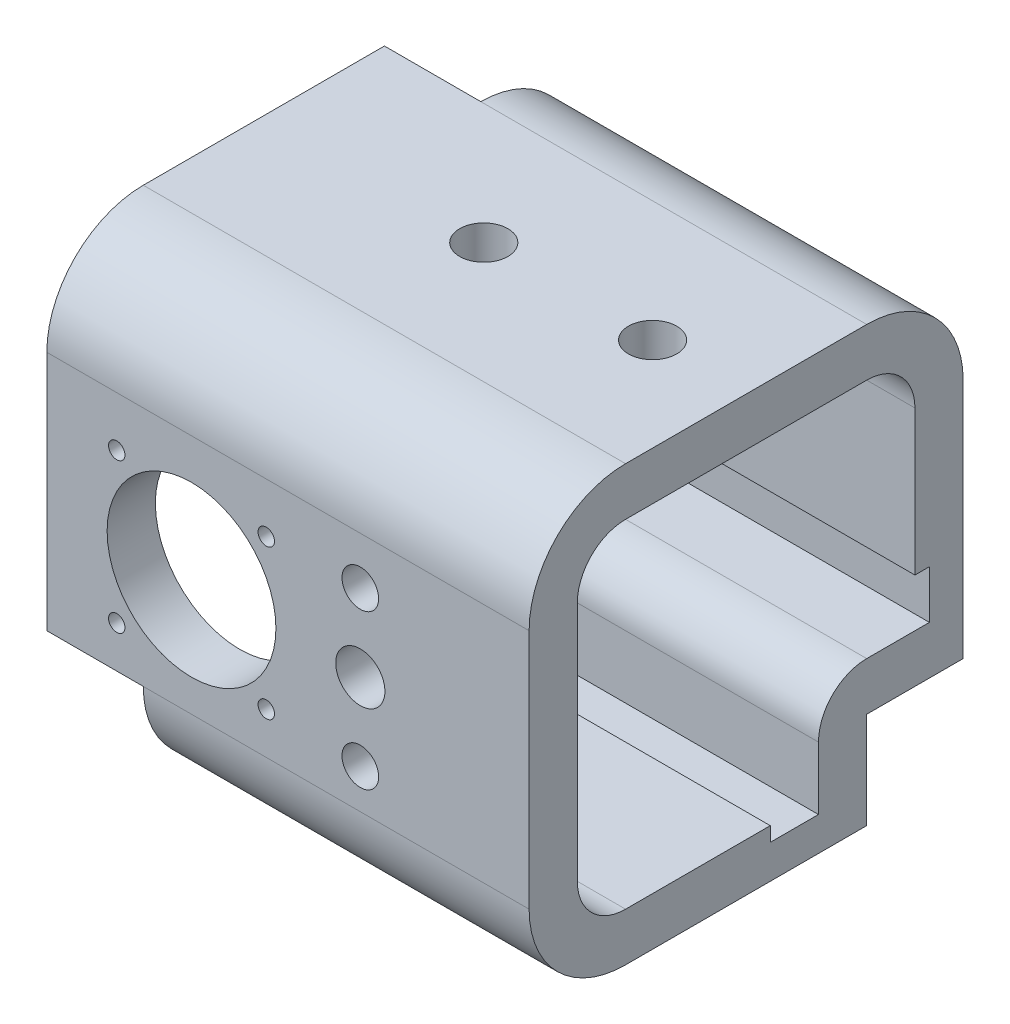
SolidWorks part; units mm, degrees
material "ABS"
ref_plane "Front Plane" through (0, 0, 0) normal (0, 0, 1) x (1, 0, 0)
ref_plane "Top Plane" through (0, 0, 0) normal (0, 1, 0) x (1, 0, 0)
ref_plane "Right Plane" through (0, 0, 0) normal (1, 0, 0) x (0, 0, -1)
sketch "Sketch2" plane through (0, 0, 0) normal (1, 0, 0) x (0, 0, -1)
  line L0 (-40.8, -13.55) -> (-40.8, -17.45) construction
  line L1 (19.2, 35.85) -> (-30.8, 35.85)
  line L2 (29.2, 25.85) -> (29.2, -24.15)
  line L3 (19.2, -34.15) -> (-30.8, -34.15)
  line L4 (-40.8, 25.85) -> (-40.8, -24.15)
  line L5 (-50.8, 15) -> (-40.8, 15) construction
  line L10 (-48.05, 15) -> (-59.05, 15) construction
  line L11 (-50.8, -15) -> (-40.8, -15) construction
  line L12 (-59.05, -15) -> (-48.05, -15) construction
  line L13 (19.2, 45.85) -> (-30.8, 45.85)
  line L14 (-50.8, 25.85) -> (-50.8, -24.15)
  line L15 (19.2, -44.15) -> (-30.8, -44.15)
  line L16 (39.2, 25.85) -> (39.2, -24.15)
  line L19 (-40.05, -21.15) -> (-29.05, -21.15) construction
  arc A0 (-30.8, 35.85) -> (-40.8, 25.85) centre (-30.8, 25.85) ccw
  arc A1 (-30.8, -34.15) -> (-40.8, -24.15) centre (-30.8, -24.15) cw
  arc A2 (19.2, -34.15) -> (29.2, -24.15) centre (19.2, -24.15) ccw
  arc A3 (19.2, 35.85) -> (29.2, 25.85) centre (19.2, 25.85) cw
  arc A4 (-30.8, 45.85) -> (-50.8, 25.85) centre (-30.8, 25.85) ccw
  arc A5 (-30.8, -44.15) -> (-50.8, -24.15) centre (-30.8, -24.15) cw
  arc A6 (19.2, -44.15) -> (39.2, -24.15) centre (19.2, -24.15) ccw
  arc A7 (19.2, 45.85) -> (39.2, 25.85) centre (19.2, 25.85) cw
  arc A8 (19.2, 35.85) -> (29.2, 25.85) centre (19.2, 25.85) cw construction
  dimension "D1" = 10
  dimension "D2" = 10
  dimension "D3" = 3
  dimension "D4" = 70
extrude "Boss-Extrude1" add sketch "Sketch2" along normal blind 70 and the other way blind 30
sketch "Sketch3" plane through (0, 0, 50.8) normal (0, 0, 1) x (1, 0, 0)
  arc A0 (-14.0466, 5.2624) -> (-13.6647, 6.1867) centre (0, 0) ccw construction
  arc A1 (-14.0466, 5.2624) -> (-13.6647, 6.1867) centre (0, 0) ccw construction
  circle A2 centre (15.5, -15.5) radius 1.7 construction
  circle A3 centre (15.5, 15.5) radius 1.7 construction
  circle A4 centre (-15.5, 15.5) radius 1.7 construction
  circle A5 centre (-15.5, -15.5) radius 1.7 construction
  circle A6 centre (15.5, -15.5) radius 1.7
  circle A7 centre (15.5, 15.5) radius 1.7
  circle A8 centre (-15.5, 15.5) radius 1.7
  circle A9 centre (-15.5, -15.5) radius 1.7
  circle A10 centre (0, 0) radius 17.5
  arc A11 (-16.3877, 6.1395) -> (-15.9422, 7.2178) centre (0, 0) ccw construction
  circle A12 centre (35, 0) radius 5.1 construction
  circle A13 centre (35, 0) radius 5.1
  circle A14 centre (35, -16) radius 3.8 construction
  circle A15 centre (35, 16) radius 3.8 construction
  circle A16 centre (35, -16) radius 3.8
  circle A17 centre (35, 16) radius 3.8
  dimension "D1" = 2.5
extrude "Cut-Extrude1" cut sketch "Sketch3" against normal up to next
sketch "Sketch4" plane through (0, 45.85, 0) normal (0, 1, 0) x (1, 0, 0)
  line L0 (50.6, -5.8) -> (15.6, -5.8) construction
  line L1 (-30, 19.2) -> (70, 19.2) construction
  line L2 (-30, -30.8) -> (70, -30.8) construction
  line L3 (28.05, -18.9) -> (38.15, -18.9) construction
  line L4 (28.05, -18.9) -> (38.15, -18.9) construction
  line L5 (33.1, -18.9) -> (33.1, -5.8) construction
  circle A0 centre (15.6, -5.8) radius 5
  circle A1 centre (50.6, -5.8) radius 5
  point P12 (33.1, -5.8)
  dimension "D1" = 10
  dimension "D2" = 35
extrude "Cut-Extrude2" cut sketch "Sketch4" against normal up to next
sketch "Sketch5" plane through (0, 0, 50.8) normal (0, 0, 1) x (1, 0, 0)
  line L0 (-30, -24.15) -> (70, -24.15) construction
  line L1 (-10, -24.15) -> (-30, -24.15)
  line L2 (-10, -24.15) -> (-10, -44.15)
  line L3 (-10, -44.15) -> (-30, -44.15)
  line L4 (-30, -24.15) -> (-30, -44.15)
  line L5 (-30, 25.85) -> (-30, -24.15) construction
  line L6 (-30, -44.15) -> (70, -44.15) construction
  dimension "D1" = 20
extrude "Cut-Extrude3" cut sketch "Sketch5" against normal through all both and the other way through all
sketch "Sketch6" plane through (0, 45.85, 0) normal (0, 1, 0) x (1, 0, 0)
  line L0 (-30, 19.2) -> (-30, -30.8) construction
  line L1 (-30, 39.2) -> (-10, 39.2)
  line L2 (-30, 39.2) -> (-30, 19.2)
  line L3 (-30, 19.2) -> (-10, 19.2)
  line L4 (-10, 39.2) -> (-10, 19.2)
  line L5 (-30, 19.2) -> (70, 19.2) construction
  line L6 (-30, 39.2) -> (70, 39.2) construction
  dimension "D1" = 20
extrude "Cut-Extrude4" cut sketch "Sketch6" against normal through all
sketch "Sketch7" plane through (-10, 0, 0) normal (-1, 0, 0) x (0, 0, 1)
  line L10 (-19.2, -44.15) -> (30.8, -44.15) construction
  line L11 (-39.2, -24.15) -> (-19.2, -24.15)
  line L12 (-39.2, -24.15) -> (-39.2, -44.15)
  line L13 (-39.2, -44.15) -> (-19.2, -44.15)
  line L14 (-19.2, -24.15) -> (-19.2, -44.15)
  line L15 (-39.2, -24.15) -> (-39.2, 25.85) construction
  line L16 (-29.2, 25.85) -> (-29.2, -24.15) construction
  line L17 (-29.2, -4.15) -> (-32.2, -4.15)
  line L18 (-29.2, -4.15) -> (-29.2, -24.15)
  line L19 (-29.2, -24.15) -> (-32.2, -24.15)
  line L20 (-32.2, -4.15) -> (-32.2, -24.15)
  line L21 (-19.2, -34.15) -> (30.8, -34.15) construction
  line L22 (-19.2, -37.15) -> (0.8, -37.15)
  line L23 (-19.2, -37.15) -> (-19.2, -34.15)
  line L24 (-19.2, -34.15) -> (0.8, -34.15)
  line L25 (0.8, -37.15) -> (0.8, -34.15)
  point P4 (0, 0)
  arc M8 (-19.2, -34.15) -> (-29.2, -24.15) centre (-19.2, -24.15) cw
  arc M14 (-39.2, -24.15) -> (-19.2, -44.15) centre (-19.2, -24.15) ccw
  dimension "D1" = 20
  dimension "D2" = 20
  dimension "D3" = 3
extrude "Cut-Extrude5" cut sketch "Sketch7" against normal through all contours L14 L11 M8 M14 | L18 L17 L20 L19 | L23 L22 L25 L24 region at (-10, -34.053, -29.103)
sketch "Sketch8" plane through (-10, 0, 0) normal (-1, 0, 0) x (0, 0, 1)
  line L0 (-39.2, -14.15) -> (-19.2, -14.15)
  line L1 (-39.2, -24.15) -> (-39.2, 25.85) construction
  line L2 (-9.2, -24.15) -> (-9.2, -44.15)
  line L3 (-19.2, -44.15) -> (30.8, -44.15) construction
  line L4 (-39.2, -24.15) -> (-19.2, -24.15)
  line L5 (-19.2, -24.15) -> (-19.2, -44.15)
  line L8 (-39.2, -14.15) -> (-39.2, -24.15)
  line L9 (-19.2, -44.15) -> (-9.2, -44.15)
  line L10 (-9.2, -14.15) -> (-9.2, -44.15) construction
  line L11 (-39.2, -14.15) -> (-9.2, -14.15) construction
  line L12 (-39.2, -24.15) -> (-32.2, -24.15) construction
  line L13 (-19.2, -37.15) -> (-19.2, -44.15) construction
  arc A0 (-9.2, -24.15) -> (-19.2, -14.15) centre (-19.2, -24.15) ccw
  point P10 (-39.725, -24.7135)
  dimension "D2" = 10
  dimension "D1" = 10
extrude "Boss-Extrude2" add sketch "Sketch8" against normal up to surface (80 mm away) up to face at (70, -3.1393, 1.8107)
